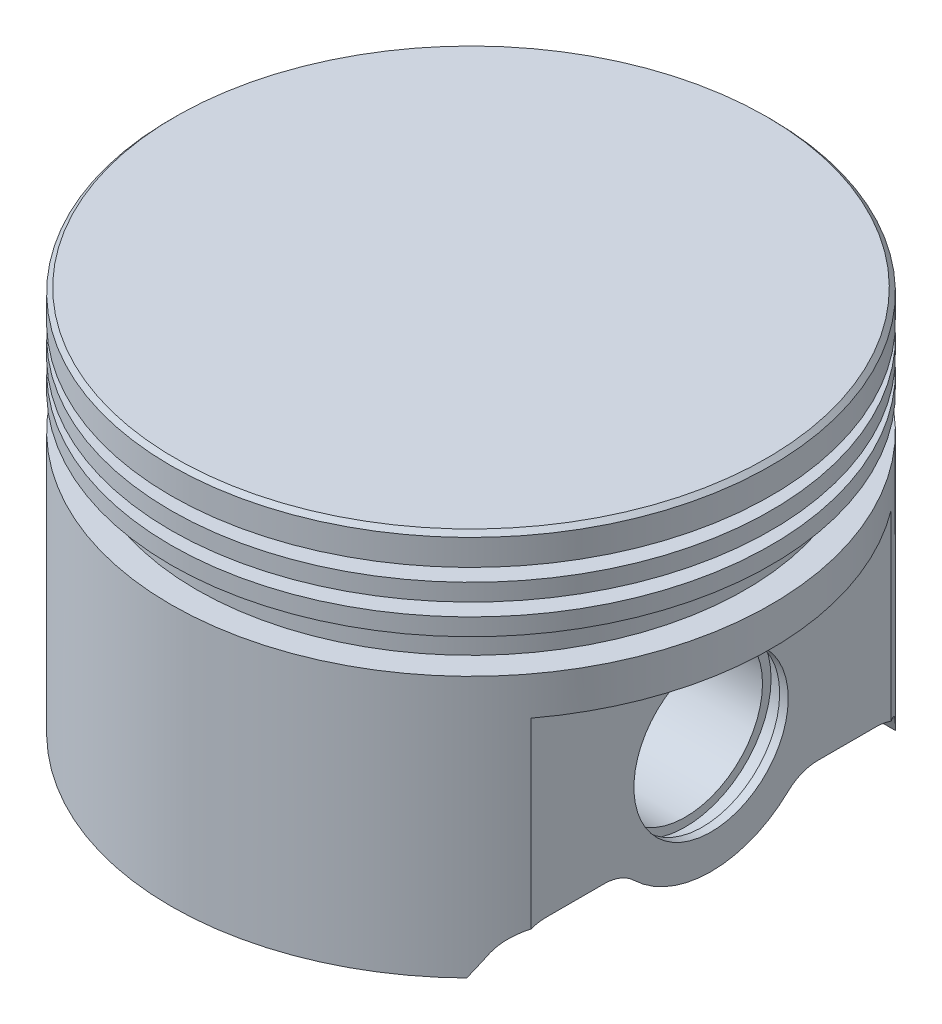
SolidWorks part; units mm, degrees
ref_plane "Front Plane" through (0, 0, 0) normal (0, 0, 1) x (1, 0, 0)
ref_plane "Top Plane" through (0, 0, 0) normal (0, 1, 0) x (1, 0, 0)
ref_plane "Right Plane" through (0, 0, 0) normal (1, 0, 0) x (0, 0, -1)
sketch "Sketch1" plane through (0, 0, 0) normal (0, 0, 1) x (1, 0, 0)
  line L0 (0, 0) -> (34.5, 0)
  line L1 (35, -0.5) -> (35, -3.5301)
  line L2 (35, -45) -> (32, -45)
  line L3 (32, -45) -> (32, -23.4608)
  line L4 (32, -23.4608) -> (25, -17)
  line L5 (25, -17) -> (25, -7)
  line L6 (25, -7) -> (0, -7)
  line L7 (0, -7) -> (0, 0)
  line L8 (35, -5.0301) -> (35, -7.0301)
  line L9 (35, -5.0301) -> (32, -5.0301)
  line L11 (35, -3.5301) -> (32, -3.5301)
  line L12 (32, -5.0301) -> (32, -3.5301)
  line L13 (35, -7.0301) -> (32, -7.0301)
  line L15 (35, -8.5301) -> (32, -8.5301)
  line L16 (32, -7.0301) -> (32, -8.5301)
  line L17 (35, -10.5301) -> (32, -10.5301)
  line L19 (35, -14.5301) -> (32, -14.5301)
  line L20 (32, -10.5301) -> (32, -14.5301)
  line L21 (35, -8.5301) -> (35, -10.5301)
  line L22 (35, -14.5301) -> (35, -45)
  line L23 (34.5, 0) -> (35, -0.5)
  point P1 (35, 0)
  dimension "D1" = 35
  dimension "D2" = 45
  dimension "D3" = 7
  dimension "D4" = 10
  dimension "D5" = 21.5392
  dimension "D6" = 3
  dimension "D7" = 10
  dimension "D8" = 3.5301
  dimension "D9" = 2
  dimension "D10" = 2
  dimension "D11" = 1.5
  dimension "D12" = 1.5
  dimension "D13" = 4
  dimension "D14" = 3
  dimension "D15" = 3
  dimension "D16" = 3
revolve "Revolve6" add sketch "Sketch1" angle 360 about L7
sketch "Sketch2" plane through (0, -45, 0) normal (0, -1, 0) x (1, 0, 0)
  line L0 (-25, 19.975) -> (-25, 12)
  line L1 (-25, 12) -> (-12, 12)
  line L2 (-9, 9) -> (-9, -9)
  line L3 (-12, -12) -> (-25, -12)
  line L4 (-25, -12) -> (-25, -19.975)
  line L5 (0, 0) -> (0, 25) construction
  line L6 (25, 19.975) -> (25, 12)
  line L7 (25, 12) -> (12, 12)
  line L8 (9, 9) -> (9, -9)
  line L9 (12, -12) -> (25, -12)
  line L10 (25, -12) -> (25, -19.975)
  circle A0 centre (0, 0) radius 32 construction
  arc A1 (-25, 19.975) -> (-25, -19.975) centre (0, 0) ccw
  arc A2 (-9, -9) -> (-12, -12) centre (-12, -9) cw
  arc A3 (-12, 12) -> (-9, 9) centre (-12, 9) cw
  circle A4 centre (0, 0) radius 25 construction
  arc A5 (12, 12) -> (9, 9) centre (12, 9) ccw
  arc A6 (9, -9) -> (12, -12) centre (12, -9) ccw
  arc A7 (25, 19.975) -> (25, -19.975) centre (0, 0) cw
  point P10 (-9, -12)
  point P13 (-9, 12)
  point P14 (-9, 0)
  dimension "D4" = 3
  dimension "D1" = 9
  dimension "D2" = 25
  dimension "D3" = 24
extrude "Boss-Extrude1" add sketch "Sketch2" against normal up to next
sketch "Sketch3" plane through (0, -45, 0) normal (0, -1, 0) x (1, 0, 0)
  line L0 (-28, 21) -> (-28, -21)
  line L1 (28, 21) -> (28, -21)
  line L2 (-25, 12) -> (-25, 19.975) construction
  line L3 (25, 19.975) -> (25, 12) construction
  circle A0 centre (0, 0) radius 35 construction
  arc A1 (-28, 21) -> (-28, -21) centre (0, 0) ccw
  arc A2 (28, -21) -> (28, 21) centre (0, 0) ccw
  dimension "D1" = 3
  dimension "D2" = 3
extrude "Cut-Extrude1" cut sketch "Sketch3" against normal blind 26 and the other way through all
sketch "Sketch4" plane through (28, 0, 0) normal (1, 0, 0) x (0, 0, -1)
  line L0 (0, -45) -> (0, -19) construction
  line L1 (-21, -45) -> (21, -45) construction
  line L2 (-21, -19) -> (21, -19) construction
  line L3 (25, -45) -> (-25, -45)
  line L4 (-35, -45) -> (-21, -45) construction
  line L5 (-25, -45) -> (-23.6721, -42.5884)
  line L6 (-19.2922, -40) -> (-12.4499, -40)
  line L7 (25, -45) -> (23.6721, -42.5884)
  line L8 (19.2922, -40) -> (12.4499, -40)
  circle A0 centre (0, -32) radius 9
  arc A1 (-8.9916, -41.3889) -> (8.9916, -41.3889) centre (0, -32) ccw
  arc A2 (-23.6721, -42.5884) -> (-19.2922, -40) centre (-19.2922, -45) cw
  arc A3 (-12.4499, -40) -> (-8.9916, -41.3889) centre (-12.4499, -45) cw
  arc A4 (23.6721, -42.5884) -> (19.2922, -40) centre (19.2922, -45) ccw
  arc A5 (12.4499, -40) -> (8.9916, -41.3889) centre (12.4499, -45) ccw
  point P15 (-22.247, -40)
  point P18 (-10.247, -40)
  dimension "D1" = 18
  dimension "D5" = 5
  dimension "D6" = 13
  dimension "D2" = 50
  dimension "D3" = 12
  dimension "D4" = 5
extrude "Cut-Extrude5" cut sketch "Sketch4" against normal through all contours A3 L6 A2 L7 L1 A1 | L8 A5 A1 L3 L2 A4 | L7 A4 L2 L3 | A2 L5 L3 L7 | L0 A0 | A0 L0 region at (28, -32, 3.8197) region at (28, -32, -3.8197) region at (28, -42.828, -15.1499) region at (28, -42.828, 15.1499)
sketch "Sketch5" plane through (28, 0, 0) normal (1, 0, 0) x (0, 0, -1)
  circle A0 centre (0, -32) radius 10
  dimension "D1" = 20
extrude "Cut-Extrude6" cut sketch "Sketch5" against normal blind 2 from offset 1 offset against normal yes
mirror "Mirror1" about plane through (0, 0, 0) normal (1, 0, 0) of "Cut-Extrude6"
